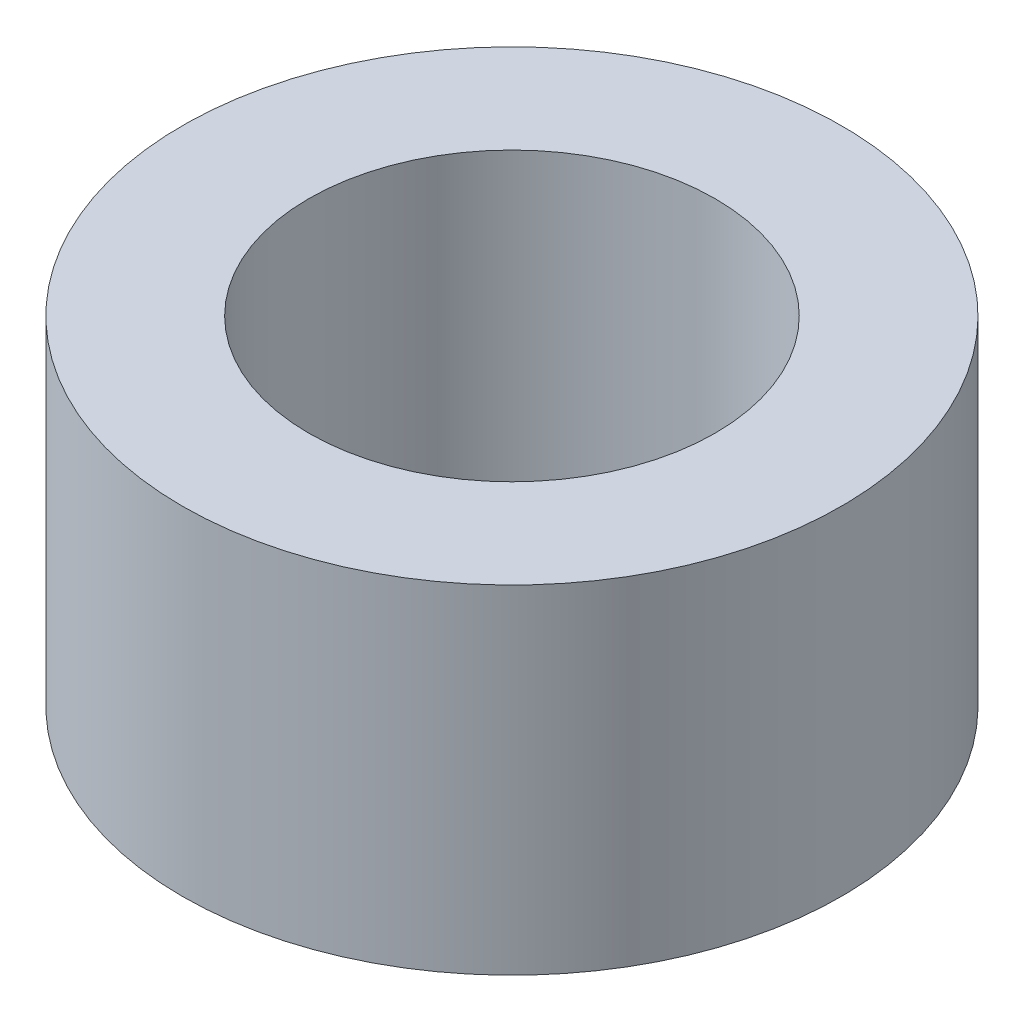
SolidWorks part; units mm, degrees
ref_plane "Front Plane" through (0, 0, 0) normal (0, 0, 1) x (1, 0, 0)
ref_plane "Top Plane" through (0, 0, 0) normal (0, 1, 0) x (1, 0, 0)
ref_plane "Right Plane" through (0, 0, 0) normal (1, 0, 0) x (0, 0, -1)
sketch "Sketch1" plane through (0, 0, 0) normal (0, 1, 0) x (1, 0, 0)
  circle A0 centre (0, 0) radius 7.5
  dimension "SLEEVE_OD" = 15
extrude "Boss-Extrude1" add sketch "Sketch1" along normal blind 7.6909
sketch "Sketch2" plane through (0, 0, 0) normal (0, 1, 0) x (1, 0, 0)
  circle A0 centre (0, 0) radius 4.6236
  dimension "BORE_D" = 9.2472
extrude "Cut-Extrude1" cut sketch "Sketch2" along normal through all
chamfer "Chamfer1" distance 1.2192 angle 61.335 rebuild error yes
